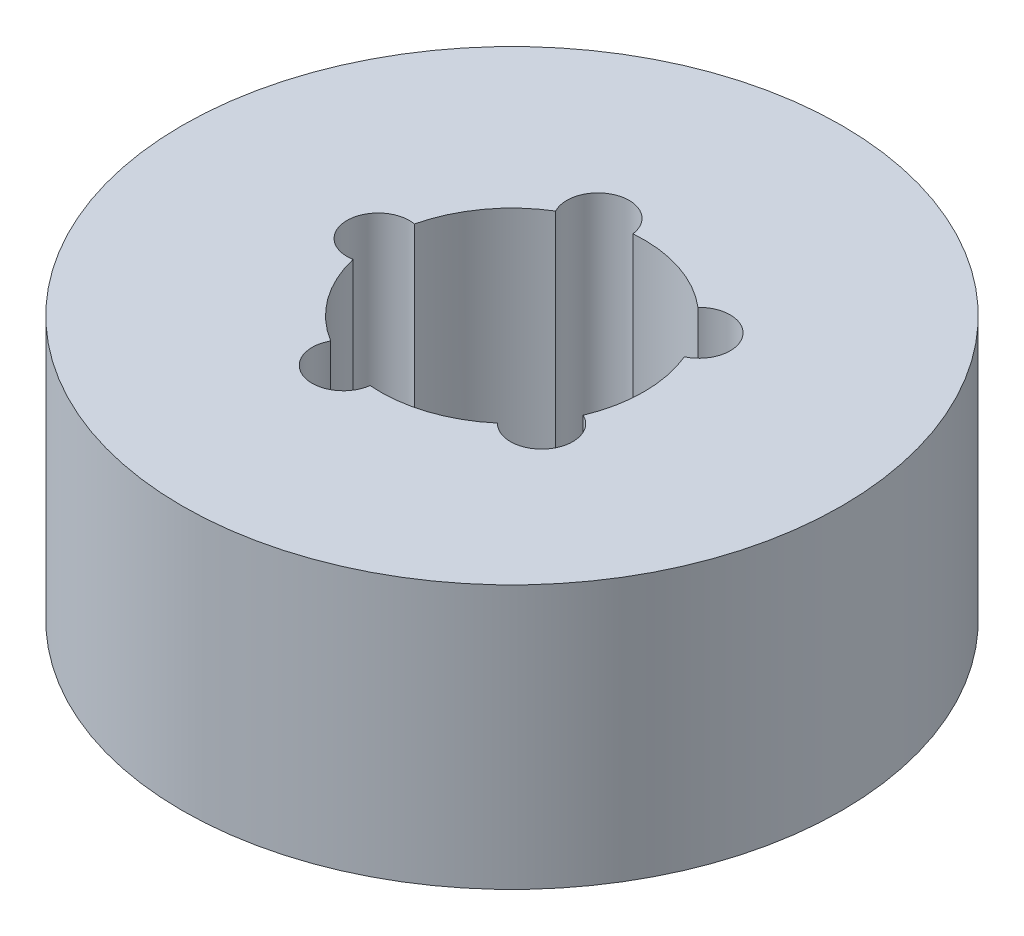
SolidWorks part; units mm, degrees
ref_plane "Front Plane" through (0, 0, 0) normal (0, 0, 1) x (1, 0, 0)
ref_plane "Top Plane" through (0, 0, 0) normal (0, 1, 0) x (1, 0, 0)
ref_plane "Right Plane" through (0, 0, 0) normal (1, 0, 0) x (0, 0, -1)
sketch "Sketch1" plane through (0, 0, 0) normal (0, 1, 0) x (1, 0, 0)
  circle A0 centre (0, 0) radius 25
  dimension "FLANGE_OD" = 50
extrude "Boss-Extrude1" add sketch "Sketch1" along normal blind 20
sketch "Sketch2" plane through (0, 0, 0) normal (0, 1, 0) x (1, 0, 0)
  circle A0 centre (0, 0) radius 10
  dimension "BORE_D" = 20
extrude "Cut-Extrude1" cut sketch "Sketch2" along normal through all
sketch "Sketch3" plane through (0, 20, 0) normal (0, 1, 0) x (1, 0, 0)
  circle A0 centre (0, 0) radius 10.1497 construction
  circle A1 centre (-10.1497, 0) radius 2.3653
  dimension "BOLT_D" = 4.7307
  dimension "BOLT_PCD" = 20.2993
extrude "Cut-Extrude2" cut sketch "Sketch3" against normal blind 16.7173
pattern_circular "CirPattern1" count 5 over 360 about axis through (0, 0, 0) along (0, 1, 0) of "Cut-Extrude2"
